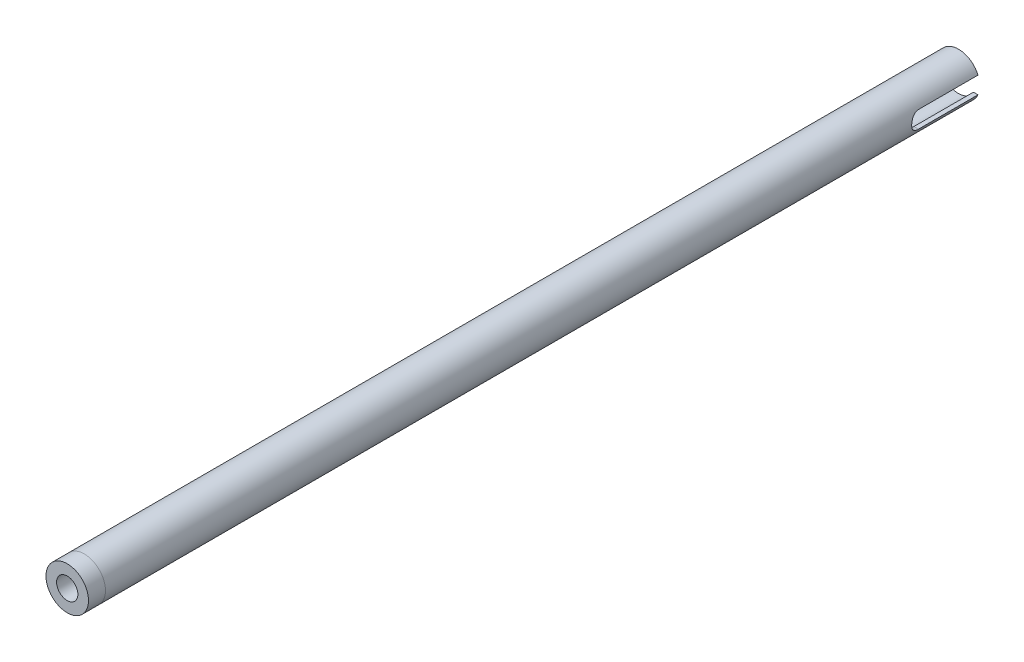
SolidWorks part; units mm, degrees
ref_plane "Front Plane" through (0, 0, 0) normal (0, 0, 1) x (1, 0, 0)
ref_plane "Top Plane" through (0, 0, 0) normal (0, 1, 0) x (1, 0, 0)
ref_plane "Right Plane" through (0, 0, 0) normal (1, 0, 0) x (0, 0, -1)
sketch "Axis" plane through (0, 0, 0) normal (0, 1, 0) x (1, 0, 0)
  line L0 (0, 0) -> (0, 332.6364) construction
  line L1 (0, 0) -> (0, -28.575) construction
  line L2 (0, 332.6364) -> (-7.9375, 332.6364) construction
  line L3 (0, 361.3979) -> (-10.3187, 324.008) construction
  dimension "D1" = 28.575
  dimension "D2" = 7.9375
sketch "Sketch1" plane through (0, 0, 0) normal (0, 0, 1) x (1, 0, 0)
  line L0 (-7.9375, 0) -> (7.9375, 0) construction
  line L1 (-7.2748, 3.175) -> (7.2748, 3.175)
  line L2 (-7.2748, -3.175) -> (7.2748, -3.175)
  circle A0 centre (0, 0) radius 7.9375
  circle A1 centre (0, 0) radius 6.4135
  circle A2 centre (0, 0) radius 3.9688
  dimension "D1" = 15.875
  dimension "D3" = 7.9375
  dimension "D2" = 1.524
  dimension "D4" = 6.35
extrude "Threaded insert 1-1" add sketch "Sketch1" against normal blind 6.35 contours A2 L1 A1 | A1 L1 A0 | A2 L0 A1 L1 | A1 L0 A0 L1 | L0 A1 L2 A0 | L0 A2 L2 A1 | A2 L2 A1 | A1 L2 A0 | L0 A1 L2 A2 | L0 A0 L2 A1 | A0 L0 A1 L1 | A1 L0 A2 L1 region at (4.7887, 1.6543, 0) region at (4.7887, -1.6543, 0) region at (6.9234, 1.6163, 0) region at (6.9234, -1.6163, 0) region at (-4.7887, -1.6543, 0) region at (-4.7887, 1.6543, 0) region at (0, 4.6159, 0) region at (0, -4.6159, 0) region at (0, 6.5666, 0) region at (6.4237, -3.3281, 0) region at (-6.9234, -1.6163, 0) region at (-6.9234, 1.6163, 0)
extrude "Threaded insert 1-2" add sketch "Sketch1<3>" against normal blind 9.525 from surface contours A2 L1 A1 | A2 L0 A1 L1 | L0 A2 L2 A1 | A2 L2 A1 | L0 A1 L2 A2 | A1 L0 A2 L1 region at (4.7887, 1.6543, 0) region at (4.7887, -1.6543, 0) region at (-4.7887, -1.6543, 0) region at (-4.7887, 1.6543, 0) region at (0, 4.6159, 0) region at (0, -4.6159, 0) starting at face at (7.9375, 0, -6.35)
sketch "Sketch1<3>" plane through (0, 0, 0) normal (0, 0, 1) x (1, 0, 0) same geometry as "Sketch1"
extrude "A-arm tube" add sketch "Sketch1<4>" against normal up to vertex (332.6364 mm away) from surface separate body contours A1 L1 A0 | A1 L0 A0 L1 | L0 A1 L2 A0 | A1 L2 A0 | L0 A0 L2 A1 | A0 L0 A1 L1 region at (6.9234, 1.6163, 0) region at (6.9234, -1.6163, 0) region at (0, 6.5666, 0) region at (6.4237, -3.3281, 0) region at (-6.9234, -1.6163, 0) region at (-6.9234, 1.6163, 0) up to point (0, 0, -332.6364) starting at face at (6.4135, 0, -6.35)
sketch "Sketch1<4>" plane through (0, 0, 0) normal (0, 0, 1) x (1, 0, 0) same geometry as "Sketch1"
extrude "Apex slot" cut sketch "Sketch1<5>" along normal blind 25.4 from surface contours A0 L0 A1 L1 | L0 A0 L2 A1 | A1 L0 A0 L1 | L0 A1 L2 A0 region at (6.9234, 1.6163, 0) region at (6.9234, -1.6163, 0) region at (-6.9234, -1.6163, 0) region at (-6.9234, 1.6163, 0) starting at face at (6.4135, 0, -332.6364)
sketch "Sketch1<5>" plane through (0, 0, 0) normal (0, 0, 1) x (1, 0, 0) same geometry as "Sketch1"
fillet "Fillet1" radius 3.175 4 edges at (-6.4237, 3.175, -307.2364) (-6.4237, -3.175, -307.2364) (6.4237, -3.175, -307.2364) (6.4237, 3.175, -307.2364)
equation "\"tube diameter\"= 5 / 8"
equation "\"tube thickness\"= .06"
equation "\"apex thickness\"= .25"
equation "\"tube slot\"= 1"
equation "\"D1@Sketch1\"=\"tube diameter\""
equation "\"D2@Sketch1\"=\"tube thickness\""
equation "\"threaded insert hole\"= .3125"
equation "\"D3@Sketch1\"=\"threaded insert hole\""
equation "\"D4@Sketch1\"=\"apex thickness\""
equation "\"D1@Apex slot\" = \"tube slot\""
equation "\"D1@Fillet1\"=\"apex thickness\"/2"
equation "\"D2@Axis\"=\"tube diameter\"/2"
